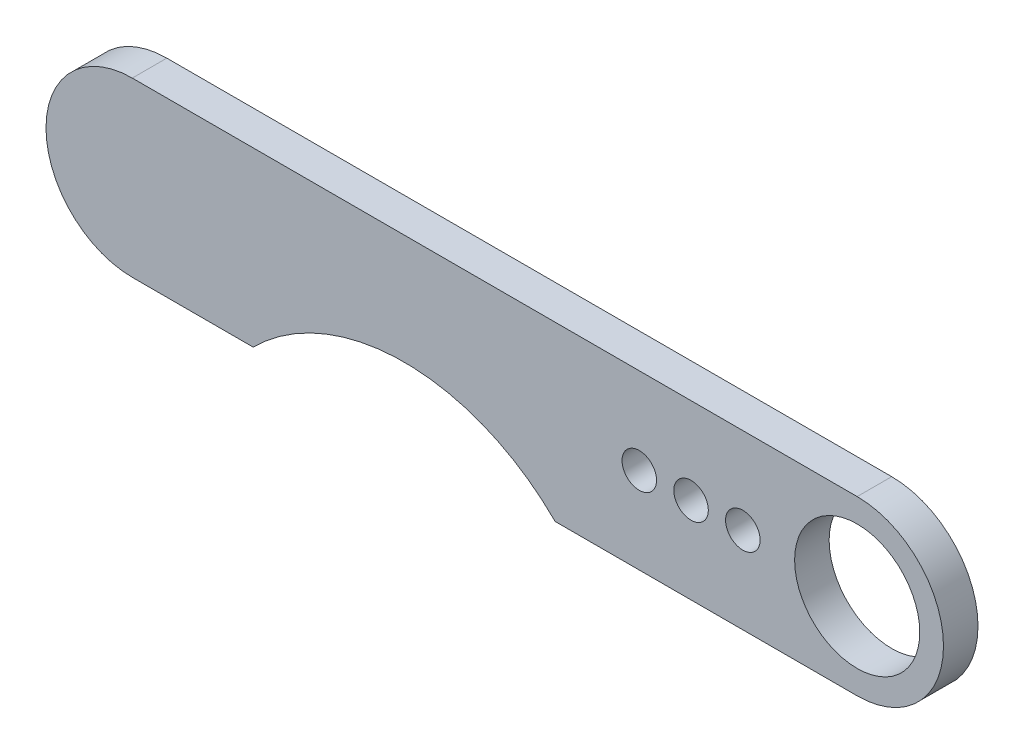
SolidWorks part; units mm, degrees
ref_plane "Front Plane" through (0, 0, 0) normal (0, 0, 1) x (1, 0, 0)
ref_plane "Top Plane" through (0, 0, 0) normal (0, 1, 0) x (1, 0, 0)
ref_plane "Right Plane" through (0, 0, 0) normal (1, 0, 0) x (0, 0, -1)
sketch "Sketch1" plane through (0, 0, 0) normal (0, 0, 1) x (1, 0, 0)
  line L0 (-42, 0) -> (0, 0) construction
  line L1 (-42, 5) -> (0, 5)
  line L2 (-42, -5) -> (0, -5)
  arc A0 (-42, 5) -> (-42, -5) centre (-42, 0) ccw
  arc A1 (0, -5) -> (0, 5) centre (0, 0) ccw
  point P2 (-21, 0)
  dimension "D1" = 42
  dimension "D2" = 10
extrude "Boss-Extrude1" add sketch "Sketch1" along normal blind 2
sketch "Sketch3" plane through (0, 0, 0) normal (0, 0, -1) x (-1, 0, 0)
  line L0 (0, 0) -> (21.8693, 0) construction
  line L1 (3.625, 0) -> (6.625, 0) construction
  line L2 (42, -5) -> (0, -5) construction
  line L3 (35, -5) -> (0, -5)
  line L4 (21.8693, 0) -> (42, 0) construction
  circle A0 centre (0, 0) radius 3.625
  circle A1 centre (6.625, 0) radius 1
  circle A3 centre (9.625, 0) radius 1
  circle A4 centre (12.625, 0) radius 1
  arc A5 (42, -5) -> (42, 5) centre (42, 0) ccw construction
  arc A6 (42, -5) -> (42, 5) centre (42, 0) ccw
  arc A7 (17.5, -5) -> (35, -5) centre (26.25, -13.75) cw
  dimension "D1" = 2
  dimension "D3" = 7.25
  dimension "D2" = 3
  dimension "D4" = 3
  dimension "D5" = 3
  dimension "D6" = 7
extrude "Cut-Extrude1" cut sketch "Sketch3" against normal up to surface (2 mm away) contours A7 L3 | A0 | A1 | A3 | A4 region at (-26.25, -3.5304, 0) up to face at (-21, 0, 2)
